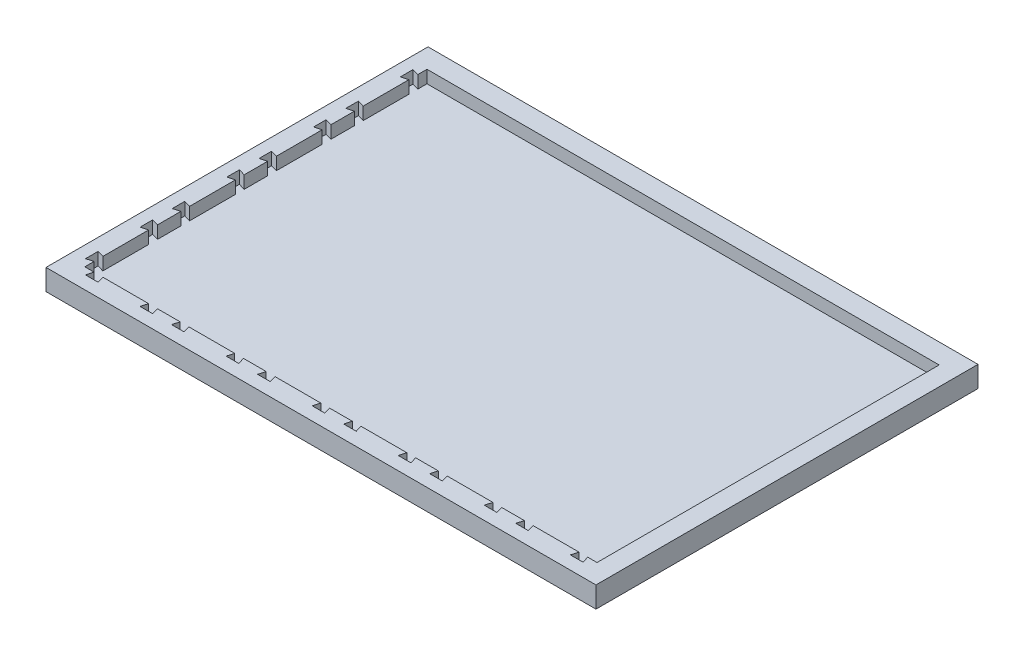
SolidWorks part; units mm, degrees
ref_plane "Front Plane" through (0, 0, 0) normal (0, 0, 1) x (1, 0, 0)
ref_plane "Top Plane" through (0, 0, 0) normal (0, 1, 0) x (1, 0, 0)
ref_plane "Right Plane" through (0, 0, 0) normal (1, 0, 0) x (0, 0, -1)
sketch "Sketch1" plane through (0, 0, 0) normal (0, 1, 0) x (1, 0, 0)
  line L1 (-65.5, -45.5) -> (65.5, -45.5)
  line L2 (-65.5, -45.5) -> (-65.5, 45.5)
  line L3 (-65.5, 45.5) -> (65.5, 45.5)
  line L4 (65.5, -45.5) -> (65.5, 45.5)
  line L5 (-65.5, -45.5) -> (65.5, 45.5) construction
  line L6 (-65.5, 45.5) -> (65.5, -45.5) construction
  point P0 (0, 0)
  dimension "D1" = 91
  dimension "D2" = 131
extrude "Boss-Extrude1" add sketch "Sketch1" along normal blind 5
sketch "Sketch3" plane through (0, 5, 0) normal (0, 1, 0) x (1, 0, 0)
  line L1 (-61, -40.75) -> (-58.8, -40.75)
  line L2 (-61, -40.75) -> (-61, -38.55)
  line L5 (-61, -40.75) -> (61, 40.75) construction
  line L6 (-61, 40.75) -> (61, -40.75) construction
  line L13 (0, -40.75) -> (0, 40.75) construction
  line L15 (-58.8, -40.75) -> (-59.25, -42.35)
  line L16 (-59.25, -42.35) -> (-56.25, -42.35)
  line L17 (-56.25, -42.35) -> (-56.7, -40.75)
  line L19 (-45.8, -40.75) -> (-46.25, -42.35)
  line L20 (-46.25, -42.35) -> (-43.25, -42.35)
  line L21 (-43.25, -42.35) -> (-43.7, -40.75)
  line L70 (-38.3, -40.75) -> (-38.75, -42.35)
  line L71 (-38.75, -42.35) -> (-35.75, -42.35)
  line L72 (-35.75, -42.35) -> (-36.2, -40.75)
  line L73 (-25.3, -40.75) -> (-25.75, -42.35)
  line L74 (-25.75, -42.35) -> (-22.75, -42.35)
  line L75 (-22.75, -42.35) -> (-23.2, -40.75)
  line L76 (-17.8, -40.75) -> (-18.25, -42.35)
  line L77 (-18.25, -42.35) -> (-15.25, -42.35)
  line L78 (-15.25, -42.35) -> (-15.7, -40.75)
  line L79 (-4.8, -40.75) -> (-5.25, -42.35)
  line L80 (-5.25, -42.35) -> (-2.25, -42.35)
  line L81 (-2.25, -42.35) -> (-2.7, -40.75)
  line L82 (2.7, -40.75) -> (2.25, -42.35)
  line L83 (2.25, -42.35) -> (5.25, -42.35)
  line L84 (5.25, -42.35) -> (4.8, -40.75)
  line L85 (15.7, -40.75) -> (15.25, -42.35)
  line L86 (15.25, -42.35) -> (18.25, -42.35)
  line L87 (18.25, -42.35) -> (17.8, -40.75)
  line L88 (23.2, -40.75) -> (22.75, -42.35)
  line L89 (22.75, -42.35) -> (25.75, -42.35)
  line L90 (25.75, -42.35) -> (25.3, -40.75)
  line L91 (36.2, -40.75) -> (35.75, -42.35)
  line L92 (35.75, -42.35) -> (38.75, -42.35)
  line L93 (38.75, -42.35) -> (38.3, -40.75)
  line L94 (43.7, -40.75) -> (43.25, -42.35)
  line L95 (43.25, -42.35) -> (46.25, -42.35)
  line L96 (46.25, -42.35) -> (45.8, -40.75)
  line L97 (56.7, -40.75) -> (56.25, -42.35)
  line L98 (56.25, -42.35) -> (59.25, -42.35)
  line L99 (59.25, -42.35) -> (58.8, -40.75)
  line L100 (-56.7, -40.75) -> (-45.8, -40.75)
  line L101 (-43.7, -40.75) -> (-38.3, -40.75)
  line L102 (-36.2, -40.75) -> (-25.3, -40.75)
  line L103 (-23.2, -40.75) -> (-17.8, -40.75)
  line L104 (-15.7, -40.75) -> (-4.8, -40.75)
  line L105 (-2.7, -40.75) -> (2.7, -40.75)
  line L106 (4.8, -40.75) -> (15.7, -40.75)
  line L107 (17.8, -40.75) -> (23.2, -40.75)
  line L108 (25.3, -40.75) -> (36.2, -40.75)
  line L109 (38.3, -40.75) -> (43.7, -40.75)
  line L110 (45.8, -40.75) -> (56.7, -40.75)
  line L111 (58.8, -40.75) -> (61, -40.75)
  line L112 (-61, 38.55) -> (-62.6, 39)
  line L113 (-62.6, 39) -> (-62.6, 36)
  line L115 (-62.6, 36) -> (-61, 36.45)
  line L116 (-61, 25.55) -> (-62.6, 26)
  line L117 (-62.6, 26) -> (-62.6, 23)
  line L118 (-62.6, 23) -> (-61, 23.45)
  line L119 (-61, 17.8833) -> (-62.6, 18.3333)
  line L120 (-62.6, 18.3333) -> (-62.6, 15.3333)
  line L121 (-62.6, 15.3333) -> (-61, 15.7833)
  line L122 (-61, 4.8833) -> (-62.6, 5.3333)
  line L123 (-62.6, 5.3333) -> (-62.6, 2.3333)
  line L124 (-62.6, 2.3333) -> (-61, 2.7833)
  line L125 (-61, -2.7833) -> (-62.6, -2.3333)
  line L126 (-62.6, -2.3333) -> (-62.6, -5.3333)
  line L127 (-62.6, -5.3333) -> (-61, -4.8833)
  line L128 (-61, -15.7833) -> (-62.6, -15.3333)
  line L129 (-62.6, -15.3333) -> (-62.6, -18.3333)
  line L130 (-62.6, -18.3333) -> (-61, -17.8833)
  line L131 (-61, -23.45) -> (-62.6, -23)
  line L132 (-62.6, -23) -> (-62.6, -26)
  line L133 (-62.6, -26) -> (-61, -25.55)
  line L134 (-61, -36.45) -> (-62.6, -36)
  line L135 (-62.6, -36) -> (-62.6, -39)
  line L136 (-62.6, -39) -> (-61, -38.55)
  line L137 (-61, 38.55) -> (-61, 40.75)
  line L138 (-61, 25.55) -> (-61, 36.45)
  line L139 (-61, 4.8833) -> (-61, 15.7833)
  line L140 (-61, -2.7833) -> (-61, 2.7833)
  line L141 (-61, -15.7833) -> (-61, -4.8833)
  line L142 (-61, -23.45) -> (-61, -17.8833)
  line L143 (-61, -36.45) -> (-61, -25.55)
  line L144 (-61, 17.8833) -> (-61, 23.45)
  line L177 (-61, 40.75) -> (61, 40.75)
  line L178 (61, -40.75) -> (61, 40.75)
  point P0 (0, 0)
  point P6 (0, 0)
  point P7 (0, 0)
  point P8 (0, 0)
  dimension "D2" = 122
  dimension "D3" = 3
  dimension "D4" = 2.2
  dimension "D5" = 0.45
  dimension "D6" = 1.6
  dimension "D7" = 0.45
  dimension "D8" = 10
  dimension "D10" = 4.5
  dimension "D11" = 81.5
  dimension "D15" = 4
  dimension "D17" = 6
extrude "Cut-Extrude2" cut sketch "Sketch3" against normal blind 3 contours L111 L178 L177 L137 L112 L113 L115 L138 L116 L117 L118 L144 L119 L120 L121 L139 L122 L123 L124 L140 L125 L126 L127 L141 L128 L129 L130 L142 L131 L132 L133 L143 L134 L135 L136 L2 L1 L15 L16 L17 L100 L19 L20 L21 L101 L70 L71 L72 L102 L73 L74 | L178 L177 L137 L112 L113 L115 L138 L116 L117 L118 L144 L119 L120 L121 L139 L122 L123 L124 L140 L125 L126 L127 L141 L128 L129 L130 L142 L131 L132 L133 L143 L134 L135 L136 L2 L1 L15 L16 L17 L100 L19 L20 L21 L101 L70 L71 L72 L102 L73 L74 L75 L103 L76 L77 L78 L104 L79 L80 L81 L105 L82 L83 L84 L106 L85 L86 L87 L107 L88 L89 L90 L108 L91 L92 L93 L109 L94 L95 L96 L110 L97 L98 L99 L111 region at (-0.2014, 5, 0.2032)
